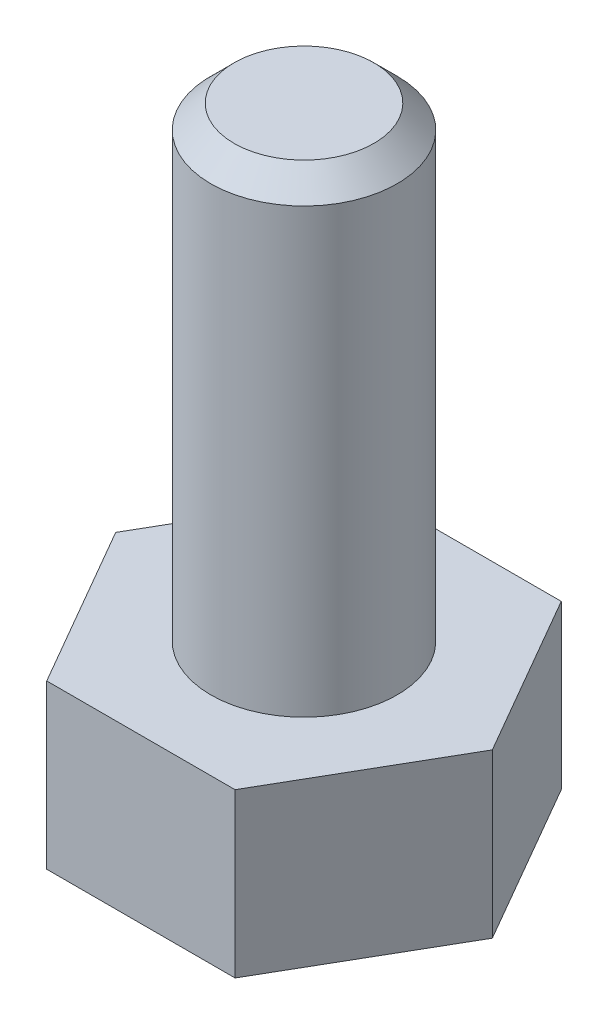
SolidWorks part; units mm, degrees
material "1.6523 (20NiCrMoS2-2)"
ref_plane "Front Plane" through (0, 0, 0) normal (0, 0, 1) x (1, 0, 0)
ref_plane "Top Plane" through (0, 0, 0) normal (0, 1, 0) x (1, 0, 0)
ref_plane "Right Plane" through (0, 0, 0) normal (1, 0, 0) x (0, 0, -1)
sketch "Sketch1" plane through (0, 0, 0) normal (0, 1, 0) x (1, 0, 0)
  line L1 (2.0207, -3.5) -> (4.0415, 0)
  line L2 (4.0415, 0) -> (2.0207, 3.5)
  line L3 (2.0207, 3.5) -> (-2.0207, 3.5)
  line L4 (-2.0207, 3.5) -> (-4.0415, 0)
  line L5 (-4.0415, 0) -> (-2.0207, -3.5)
  line L6 (-2.0207, -3.5) -> (2.0207, -3.5)
  circle A0 centre (0, 0) radius 3.5 construction
  circle A1 centre (0, 0) radius 2
  dimension "D1" = 4
  dimension "D2" = 7
extrude "Boss-Extrude1" add sketch "Sketch1" along normal blind 3.5 contours A1 | L5 L6 L1 L2 L3 L4 A1 region at (0, 0, 3.3931) region at (0, 0, 0)
extrude "Boss-Extrude2" add sketch "Sketch1<3>" along normal blind 10 from surface contours A1 region at (0, 0, 0) starting at face at (0, 3.5, 0)
sketch "Sketch1<3>" plane through (0, 0, 0) normal (0, 1, 0) x (1, 0, 0) same geometry as "Sketch1"
chamfer "Chamfer1" distance 0.5 angle 45 1 edges at (0, 13.5, 2)
